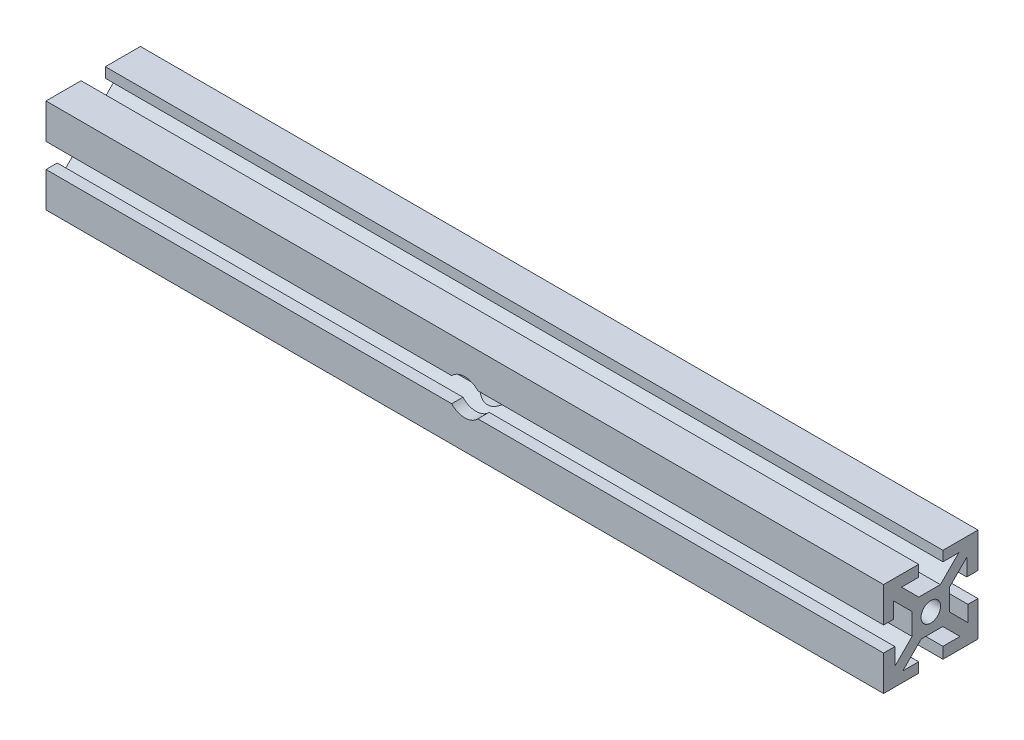
SolidWorks part; units mm, degrees
ref_plane "Front Plane" through (0, 0, 0) normal (0, 0, 1) x (1, 0, 0)
ref_plane "Top Plane" through (0, 0, 0) normal (0, 1, 0) x (1, 0, 0)
ref_plane "Right Plane" through (0, 0, 0) normal (1, 0, 0) x (0, 0, -1)
sketch "Sketch1" plane through (0, 0, 0) normal (1, 0, 0) x (0, 0, -1)
  line L0 (2.5534, 5) -> (7.4749, 9.9215)
  line L1 (-5, 5) -> (5, 5)
  line L2 (-5, 5) -> (-5, -5)
  line L3 (-5, -5) -> (5, -5)
  line L4 (5, 5) -> (5, -5)
  line L5 (-5, 5) -> (5, -5) construction
  line L6 (-5, -5) -> (5, 5) construction
  line L7 (7.4749, 9.9215) -> (9.5962, 7.8001)
  line L8 (9.5962, 7.8001) -> (5, 3.2039)
  line L9 (5, 5) -> (13.6489, 13.6489) construction
  line L10 (7.4749, 9.9215) -> (3.24, 9.9215)
  line L11 (3.24, 9.9215) -> (3.24, 12.5962)
  line L12 (3.24, 12.5962) -> (12.5962, 12.5962)
  line L13 (9.5962, 7.8001) -> (9.5962, 3.24)
  line L14 (9.5962, 3.24) -> (12.5962, 3.24)
  line L15 (12.5962, 3.24) -> (12.5962, 12.5962)
  line L17 (0, 0) -> (0, 24.089) construction
  line L18 (0, 0) -> (23.75, 0) construction
  circle A0 centre (0, 0) radius 2.605
  point P0 (0, 0)
  dimension "D1" = 5.21
  dimension "D2" = 10
  dimension "D3" = 10
  dimension "D4" = 3
  dimension "D5" = 1.27
  dimension "D6" = 6.5
  dimension "D7" = 3.24
  dimension "D8" = 3.24
  dimension "D9" = 3
extrude "Boss-Extrude1" add sketch "Sketch1" along normal blind 223.52 contours L4 L1 L2 L3 A0 | L8 L7 L0 L1 L4 | L14 L15 L12 L11 L10 L7 L13 region at (0, 4.8586, -3.7767) region at (0, 6.7479, -6.3823) region at (0, 9.18, -9.3105)
ref_axis "Axis1" through (0, 0, 0) along (1, 0, 0)
pattern_circular "CirPattern1" count 4 over 360 about axis through (0, 0, 0) along (1, 0, 0) of "Boss-Extrude1"
sketch "Sketch2" plane through (0, 0, 12.5962) normal (0, 0, 1) x (1, 0, 0)
  line L0 (0, -9.5962) -> (0, -5) construction
  circle A0 centre (111.76, 0) radius 4.765
  point P2 (0, -7.2981)
  dimension "D1" = 9.53
  dimension "D2" = 111.76
extrude "Cut-Extrude2" cut sketch "Sketch2" against normal blind 50 and the other way blind 10
